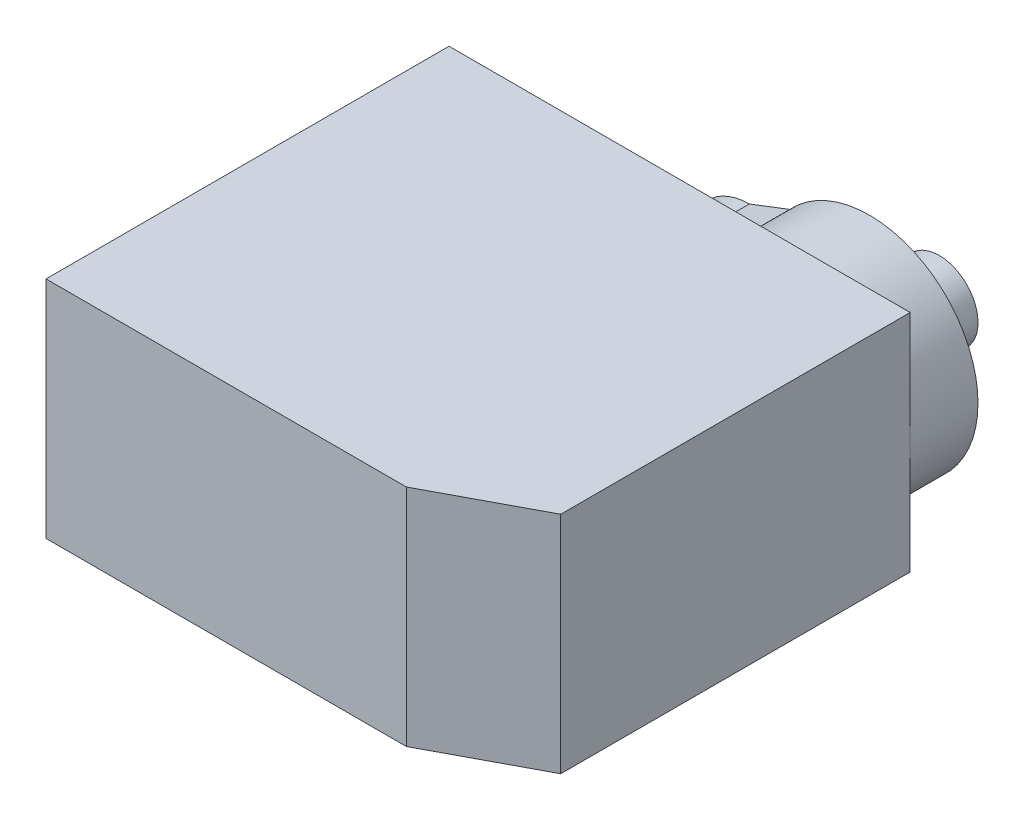
SolidWorks part; units mm, degrees
ref_plane "正面" through (0, 0, 0) normal (0, 0, 1) x (1, 0, 0)
ref_plane "平面" through (0, 0, 0) normal (0, 1, 0) x (1, 0, 0)
ref_plane "右側面" through (0, 0, 0) normal (1, 0, 0) x (0, 0, -1)
sketch "ｽｹｯﾁ1" plane through (0, 0, 0) normal (0, 1, 0) x (1, 0, 0)
  line L0 (18.6, 4.7083) -> (18.6, 0) construction
  line L1 (0, 0) -> (18.6, 0)
  line L2 (0, 0) -> (0, 20.8)
  line L3 (0, 20.8) -> (23.8, 20.8)
  line L4 (23.8, 2.7649) -> (23.8, 20.8)
  line L5 (18.6, 0) -> (23.8, 2.7649)
  dimension "D1" = 23.8
  dimension "D2" = 20.8
  dimension "D3" = 28
  dimension "D4" = 18.6
extrude "ﾎﾞｽ - 押し出し1" add sketch "ｽｹｯﾁ1" along normal blind 11.6
sketch "ｽｹｯﾁ2" plane through (0, 0, -20.8) normal (0, 0, -1) x (-1, 0, 0)
  line L0 (-18.2, 11.6) -> (-18.2, 0) construction
  line L1 (-23.8, 11.6) -> (-23.8, 0) construction
  line L2 (-23.8, 5.8) -> (0, 5.8) construction
  line L3 (0, 11.6) -> (0, 0) construction
  line L4 (-23.8, 11.6) -> (0, 11.6) construction
  line L5 (-23.8, 0) -> (0, 0) construction
  line L6 (-12, 11.6) -> (-12, 0) construction
  line L7 (-12, 9.6) -> (-14.0866, 9.6) construction
  line L8 (-14.0866, 9.6) -> (-12, 8.8)
  line L9 (-14.0866, 2) -> (-12, 2.8)
  line L10 (-14.0866, 9.6) -> (-14.0866, 2) construction
  arc A0 (-14.0866, 9.6) -> (-14.0866, 2) centre (-18.2, 5.8) ccw
  arc A1 (-12, 2.8) -> (-12, 8.8) centre (-12, 5.8) ccw
  dimension "D2" = 11.2
  dimension "D4" = 6
  dimension "D1" = 5.6
  dimension "D3" = 6.2
  dimension "D5" = 2
extrude "ﾎﾞｽ - 押し出し2" add sketch "ｽｹｯﾁ2" along normal blind 3.5
sketch "ｽｹｯﾁ3" plane through (0, 0, -24.3) normal (0, 0, -1) x (-1, 0, 0)
  line L0 (-11.2, 11.6) -> (-11.2, 0) construction
  line L1 (-23.8, 11.6) -> (0, 11.6) construction
  line L2 (-23.8, 0) -> (0, 0) construction
  line L3 (-23.8, 11.6) -> (-23.8, 5.8) construction
  line L4 (-18.2, 11.6) -> (-18.2, 0) construction
  line L5 (-23.8, 5.8) -> (0, 5.8) construction
  line L6 (-18.2, 11.6) -> (-18.2, 0) construction
  line L7 (-23.8, 5.8) -> (0, 5.8) construction
  circle A0 centre (-11.2, 5.8) radius 1
  circle A1 centre (-18.2, 5.8) radius 2.8
  dimension "D2" = 2
  dimension "D3" = 5.6
  dimension "D1" = 12.6
extrude "ﾎﾞｽ - 押し出し3" add sketch "ｽｹｯﾁ3" along normal blind 1 contours A0
extrude "ﾎﾞｽ - 押し出し4" add sketch "ｽｹｯﾁ3<3>" along normal blind 0.4
sketch "ｽｹｯﾁ3<3>" plane through (0, 0, -24.3) normal (0, 0, -1) x (-1, 0, 0) same geometry as "ｽｹｯﾁ3"
sketch "ｽｹｯﾁ5" plane through (0, 0, -24.7) normal (0, 0, -1) x (-1, 0, 0)
  line L0 (-23.8, 5.8) -> (0, 5.8) construction
  line L1 (-18.2, 11.6) -> (-18.2, 0) construction
  line L2 (-23.8, 5.8) -> (0, 5.8) construction
  line L3 (-18.2, 11.6) -> (-18.2, 0) construction
  circle A0 centre (-18.2, 5.8) radius 2
  dimension "D1" = 4
extrude "ﾎﾞｽ - 押し出し5" add sketch "ｽｹｯﾁ5" along normal blind 3.2
